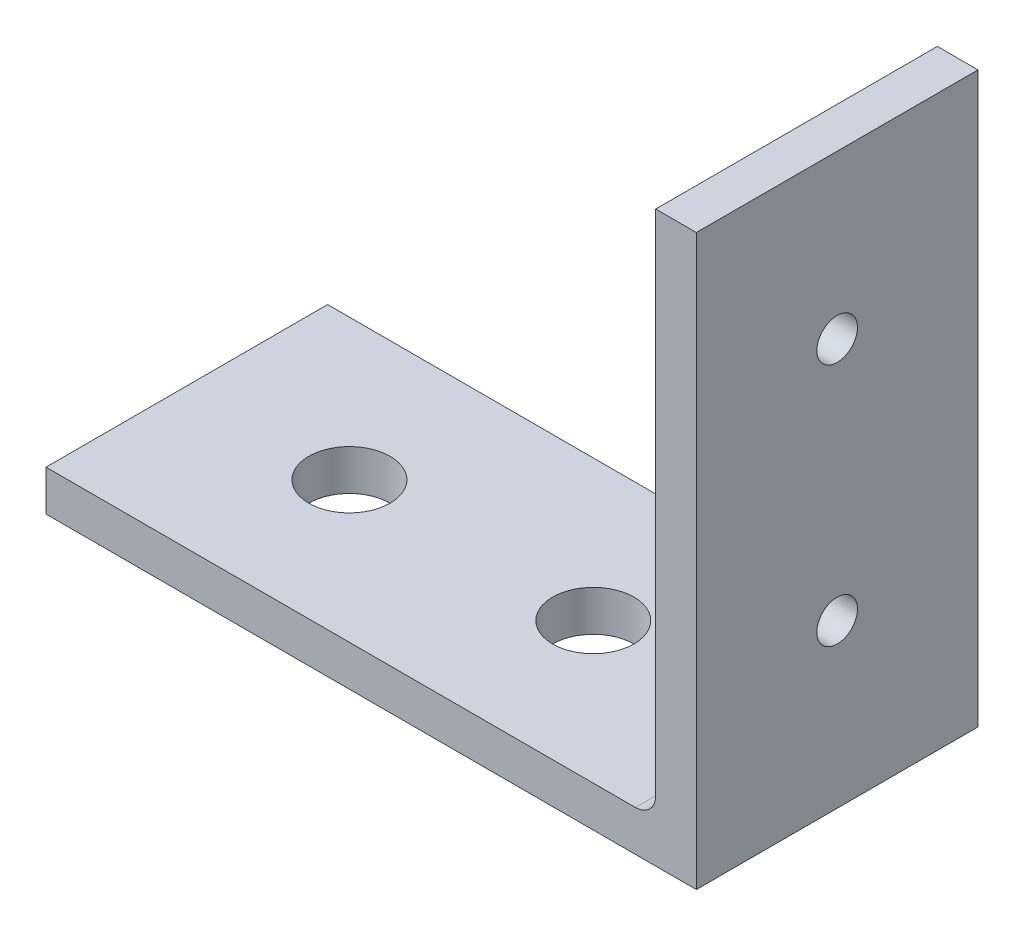
SolidWorks part; units mm, degrees
ref_plane "Front Plane" through (0, 0, 0) normal (0, 0, 1) x (1, 0, 0)
ref_plane "Top Plane" through (0, 0, 0) normal (0, 1, 0) x (1, 0, 0)
ref_plane "Right Plane" through (0, 0, 0) normal (1, 0, 0) x (0, 0, -1)
sketch "Sketch2" plane through (0, 0, 0) normal (0, 0, 1) x (1, 0, 0)
  line L0 (-25.4, 0) -> (25.4, 0)
  line L1 (25.4, 0) -> (25.4, 50.8)
  line L2 (25.4, 50.8) -> (22.225, 50.8)
  line L3 (22.225, 50.8) -> (22.225, 3.175)
  line L4 (22.225, 3.175) -> (-25.4, 3.175)
  line L5 (-25.4, 0) -> (-25.4, 3.175)
  line L6 (23.8125, 50.8) -> (25.4, 50.8) construction
  line L7 (-25.4, 1.5875) -> (-25.4, 0) construction
  dimension "Vert" = 50.8
  dimension "Horz" = 50.8
  dimension "Thickness" = 3.175
extrude "Boss-Extrude1" add sketch "Sketch2" along normal mid plane 22
fillet "Fillet1" radius 1.5875 1 edges at (22.225, 3.175, 0)
ref_plane "Contact Plane 1" through (0, 0, 0) normal (0, -1, 0) x (-1, 0, 0)
ref_plane "Contact Plane 2" through (25.4, 0, 0) normal (1, 0, 0) x (0, 0, -1)
ref_plane "Contact Plane 3" through (0, 3.175, 0) normal (0, 1, 0) x (1, 0, 0)
ref_plane "Contact Plane 4" through (22.225, 0, 0) normal (-1, 0, 0) x (0, 0, 1)
ref_plane "Contact Plane 5" through (0, 0, 11) normal (0, 0, 1) x (1, 0, 0)
ref_plane "Contact Plane 6" through (0, 0, -13.54) normal (0, 0, -1) x (-1, 0, 0)
sketch "Sketch3" plane through (0, 0, 11) normal (0, 0, 1) x (1, 0, 0)
  line L0 (-25.4, 0) -> (25.4, 0) construction
  line L1 (6.0591, 71.0024) -> (30.483, 71.0024)
  line L2 (6.0591, 71.0024) -> (6.0591, 44.45)
  line L3 (6.0591, 44.45) -> (30.483, 44.45)
  line L4 (30.483, 71.0024) -> (30.483, 44.45)
  dimension "D1" = 44.45
extrude "Cut-Extrude1" cut sketch "Sketch3" against normal through all
sketch "Sketch4" plane through (0, 0, 0) normal (0, -1, 0) x (1, 0, 0)
  line L0 (-25.4, 0) -> (-12.7, 0) construction
  line L3 (-25.4, 11) -> (-25.4, -11) construction
  line L4 (-12.7, 0) -> (6.35, 0) construction
  line L5 (6.35, 0) -> (25.4, 0) construction
  line L6 (25.4, 11) -> (25.4, -11) construction
  circle A0 centre (-12.7, 0) radius 3.175
  circle A1 centre (6.35, 0) radius 3.175
  dimension "D1" = 6.35
  dimension "D2" = 12.7
  dimension "D3" = 19.05
extrude "Cut-Extrude2" cut sketch "Sketch4" against normal through all
sketch "Sketch5" plane through (25.4, 0, 0) normal (1, 0, 0) x (0, 0, -1)
  line L0 (0, 0) -> (0, 12.7) construction
  line L1 (0, 12.7) -> (0, 31.75) construction
  line L2 (0, 31.75) -> (0, 44.45) construction
  line L3 (11, 44.45) -> (-11, 44.45) construction
  circle A0 centre (0, 31.75) radius 1.5875
  circle A1 centre (0, 12.7) radius 1.5875
  dimension "D2" = 3.175
  dimension "D1" = 12.7
extrude "Cut-Extrude3" cut sketch "Sketch5" against normal through all
equation "\"D1@Fillet1\"=\"Thickness@Sketch2\"/2"
